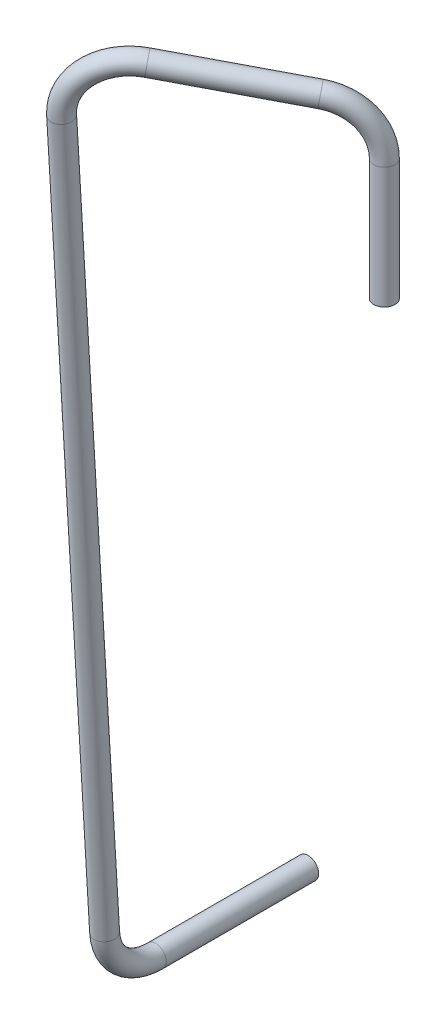
SolidWorks part; units mm, degrees
ref_plane "Piano frontale" through (0, 0, 0) normal (0, 0, 1) x (1, 0, 0)
ref_plane "Piano superiore" through (0, 0, 0) normal (0, 1, 0) x (1, 0, 0)
ref_plane "Piano destro" through (0, 0, 0) normal (1, 0, 0) x (0, 0, -1)
sketch3d "Schizzo3D1"
  line L0 (0, 0, 0) -> (0, 18.1274, 0)
  line L1 (-5.2438, 26.036, 4.32) -> (-19.4494, 28.8426, 16.0229)
  line L2 (-27.1915, 20.7587, 21.0853) -> (-32.3109, -93.4564, 9.5323)
  line L3 (-32.6332, -100.6449, 1.5728) -> (-32.6332, -100.6449, -21.2228)
  arc A0 (0, 18.1274, 0) -> (-5.2438, 26.036, 4.32) centre (-6.1745, 18.1274, 5.0867) ccw
  arc A1 (-19.4494, 28.8426, 16.0229) -> (-27.1915, 20.7587, 21.0853) centre (-20.9224, 20.9799, 16.1205) ccw
  arc A2 (-32.3109, -93.4564, 9.5323) -> (-32.6332, -100.6449, 1.5728) centre (-32.2749, -92.6529, 1.5728) ccw
  point P5 (-38.7282, -74.9416, 9.0111)
  point P6 (-43.8111, -81.7662, 11.3824)
  point P7 (-50.9369, -80.7203, -57.6692)
  point P8 (-26.3196, -100.9254, -22.107)
  point P9 (-28.3977, -100.6771, 8.7279)
  point P12 (0, 25, 0)
  point P14 (-1.0878, 18.1274, 11.2613)
  point P17 (-26.7644, 30.2878, 22.0492)
  point P18 (-15.9655, 20.1285, 22.3417)
  point P21 (-32.6332, -100.6449, 8.8052)
  point P22 (-24.283, -93.0111, 1.5728)
  point P23 (-32.5009, -100.5915, -20.4476)
  point P24 (0, 0, 0)
  point P25 (0, 0, 0)
  point P26 (-32.5301, -100.64, -20.364)
  point P27 (-32.601, -100.6371, -21.4835)
  point P28 (-32.6078, -100.6325, -21.4249)
  point P29 (-32.6189, -100.6388, -21.337)
  point P30 (-32.6332, -100.6449, -21.2228)
  dimension "D2" = 8
  dimension "D1" = 25
sweep "Sweep-Sottile2" add path "Schizzo3D1" circular profile diameter 3.17 parameters "D1"=1, "D3"=3.17
